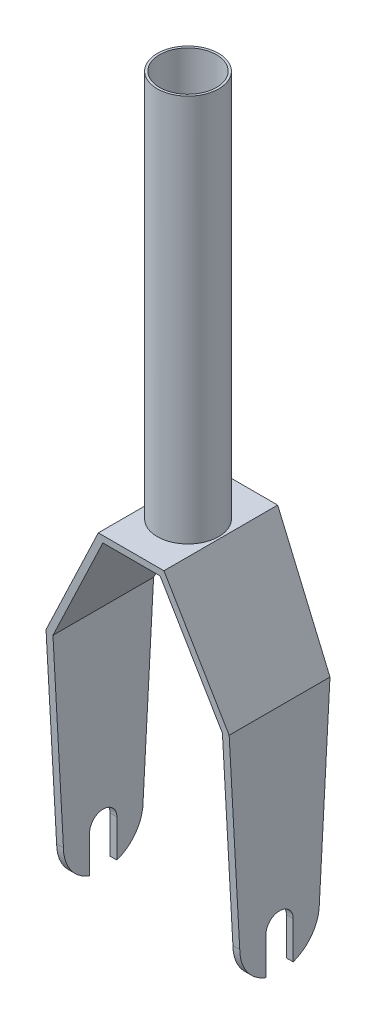
SolidWorks part; units mm, degrees
material "AISI 1035 Steel (SS)"
ref_plane "Front Plane" through (0, 0, 0) normal (0, 0, 1) x (1, 0, 0)
ref_plane "Top Plane" through (0, 0, 0) normal (0, 1, 0) x (1, 0, 0)
ref_plane "Right Plane" through (0, 0, 0) normal (1, 0, 0) x (0, 0, -1)
sketch "Sketch1" plane through (0, 0, 0) normal (0, 1, 0) x (1, 0, 0)
  circle A0 centre (0, 0) radius 13.5
  circle A1 centre (0, 0) radius 12.5
  dimension "D1" = 27
  dimension "D2" = 25
extrude "Boss-Extrude1" add sketch "Sketch1" along normal blind 175
sketch "Sketch2" plane through (0, 0, 0) normal (0, 0, 1) x (1, 0, 0)
  line L0 (13.5, 3) -> (38.75, -47)
  line L1 (13.5, 0) -> (13.5, 175) construction
  line L2 (38.75, -47) -> (38.75, -147)
  line L3 (0, 19.8827) -> (0, -145.427) construction
  line L4 (13.5, 3) -> (0, 3)
  point P10 (6.75, 3)
  dimension "D1" = 3
  dimension "D2" = 38.75
  dimension "D3" = 150
  dimension "D4" = 50
sketch "Sketch3" plane through (0, 0, 0) normal (1, 0, 0) x (0, 0, -1)
  line L1 (-25, 4.5) -> (25, 4.5)
  line L2 (-25, 4.5) -> (-25, 1.5)
  line L3 (-25, 1.5) -> (25, 1.5)
  line L4 (25, 4.5) -> (25, 1.5)
  line L7 (0, 200019.8827) -> (0, -200145.427) construction
  point P4 (0, 4.5)
  point P7 (-25, 3)
  dimension "D1" = 50
  dimension "D2" = 3
sweep "Sweep1" add profiles "Sketch3" path "Sketch2"
sketch "Sketch4" plane through (40.25, 0, 0) normal (1, 0, 0) x (0, 0, -1)
  line L0 (0, 200019.8827) -> (0, -200145.427) construction
  line L1 (-6, -130.5607) -> (-6, -147)
  line L2 (6, -130.5607) -> (6, -147)
  line L3 (25, -147) -> (-25, -147) construction
  line L4 (-17.5, -130.5607) -> (-25, 4.5)
  line L5 (-25, 4.5) -> (25, 4.5)
  line L6 (25, 4.5) -> (17.5, -130.5607)
  line L7 (-25, 4.5) -> (-25, 175)
  line L8 (-25, 175) -> (25, 175)
  line L9 (25, 175) -> (25, 4.5)
  line L10 (12.5, 175) -> (-12.5, 175) construction
  arc A0 (6, -147) -> (17.5, -130.5607) centre (0, -130.5607) ccw
  arc A1 (6, -130.5607) -> (-6, -130.5607) centre (0, -130.5607) ccw
  arc A2 (-17.5, -130.5607) -> (-6, -147) centre (0, -130.5607) ccw
  line M8 (25, -46.6427) -> (-25, -46.6427)
  dimension "D1" = 35
  dimension "D2" = 12
extrude "Cut-Extrude1" cut sketch "Sketch4" against normal blind 150 and the other way through all flip side to cut contours L6 L5 L4 M8 | L4 A2 L1 A1 L2 A0 L6 M8 | L9 L8 L7 L5 region at (40.25, -90.197, 0) region at (40.25, -20.5581, 0) region at (40.25, 89.75, 0)
mirror "Mirror1" about plane through (0, 0, 0) normal (1, 0, 0) of "Cut-Extrude1", "Sweep1"
sketch "Sketch5" plane through (0, 1.5, 0) normal (0, -1, 0) x (1, 0, 0)
  circle A0 centre (0, 0) radius 12.5
  circle A1 centre (0, 0) radius 12.5 construction
extrude "Cut-Extrude2" cut sketch "Sketch5" against normal up to next
